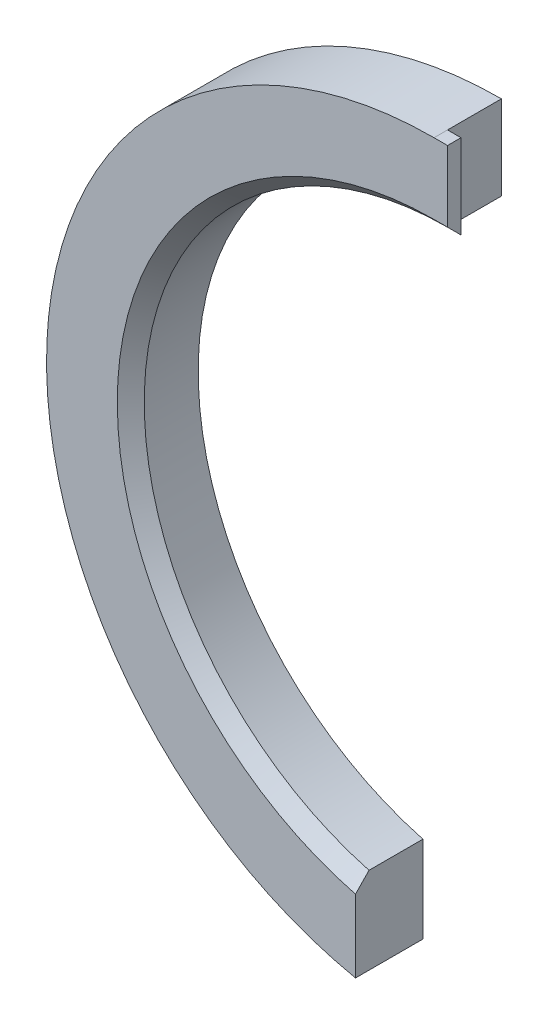
SolidWorks part; units mm, degrees
material "ABS"
ref_plane "Front Plane" through (0, 0, 0) normal (1, 0, 0) x (0, 1, 0)
ref_plane "Top Plane" through (0, 0, 0) normal (0, 0, 1) x (0, 1, 0)
ref_plane "Right Plane" through (0, 0, 0) normal (0, 1, 0) x (-1, 0, 0)
sketch "Sketch1" plane through (0, 0, 0) normal (0, 0, 1) x (0, 1, 0)
  circle A0 centre (0, 0) radius 57.5
  circle A1 centre (0, 0) radius 45
  dimension "D1" = 90
extrude "Boss-Extrude1" add sketch "Sketch1" along normal blind 10
sketch "Sketch2" plane through (0, 0, 0) normal (0, 0, -1) x (1, 0, 0)
  line L0 (0, 0) -> (0, 57.8453) construction
  line L1 (11.6505, 56.6599) -> (11.6505, 43.4657)
  line L3 (-11.6505, 43.4657) -> (-11.6505, 56.6599)
  circle A0 centre (0, 0) radius 57.8453 construction
  circle A5 centre (0, 0) radius 45 construction
  arc A10 (11.6505, 56.6599) -> (-11.6505, 56.6599) centre (0, 0) ccw
  spline S0 degree 2 poles (11.6505, 43.4657) (-0.6792, 46.4064) (-11.6505, 43.4657) knots 0 0 0 0.575547 0.575547 0.575547
  point P5 (0, 57.8453)
extrude "Cut-Extrude2" cut sketch "Sketch2" against normal blind 10
fillet "Chamfer1" radius 2 1 edges at (0, 45, 10) type face fillet profile chamfer first side face at (0, 0.6817, 10) second side face at (0, 0.7672, 5)
sketch "Sketch3" plane through (0, 0, 0) normal (0, 0, 1) x (0, 1, 0)
  line L1 (-57.4149, 0) -> (66.6982, 0)
  line L2 (-57.4149, 0) -> (-57.4149, -66.8765)
  line L3 (-57.4149, -66.8765) -> (66.6982, -66.8765)
  line L4 (66.6982, 0) -> (66.6982, -66.8765)
extrude "Cut-Extrude3" cut sketch "Sketch3" along normal blind 10
sketch "Sketch5" plane through (0, 0, 0) normal (0, 0, -1) x (1, 0, 0)
  line L0 (0, -51.25) -> (-2, -51.25) construction
  line L1 (0, -57.5) -> (0, -45) construction
  circle A0 centre (-6, -51.25) radius 4
  point P6 (0, 0)
  dimension "D2" = 8
  dimension "D1" = 2
extrude "Cut-Extrude4" cut sketch "Sketch5" against normal blind 3 from offset 2 offset against normal yes
sketch "Sketch6" plane through (0, 0, 0) normal (1, 0, 0) x (0, 1, 0)
  line L0 (45, 8) -> (47, 10)
  line L1 (47, 10) -> (57.5, 10)
  line L2 (57.5, 10) -> (57.5, 8)
  line L3 (57.5, 0) -> (57.5, 10) construction
  line L4 (57.5, 8) -> (45, 8)
extrude "Boss-Extrude2" add sketch "Sketch6" along normal blind 2
